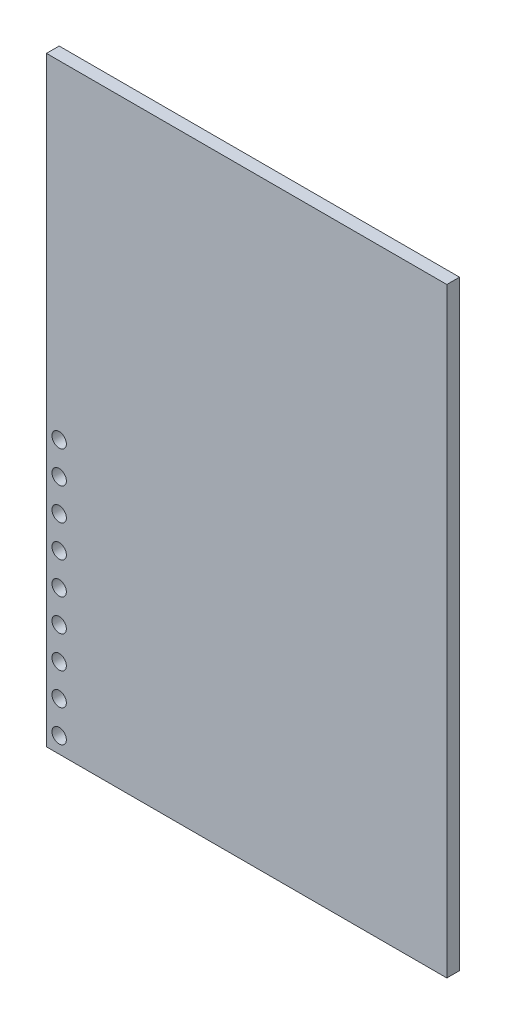
SolidWorks part; units mm, degrees
ref_plane "Front Plane" through (0, 0, 0) normal (0, 0, 1) x (1, 0, 0)
ref_plane "Top Plane" through (0, 0, 0) normal (0, 1, 0) x (1, 0, 0)
ref_plane "Right Plane" through (0, 0, 0) normal (1, 0, 0) x (0, 0, -1)
sketch "Sketch1" plane through (0, 0, 0) normal (0, 1, 0) x (1, 0, 0)
  line L1 (0, 0) -> (100, 0)
  line L2 (0, 0) -> (0, 3.175)
  line L3 (0, 3.175) -> (100, 3.175)
  line L4 (100, 0) -> (100, 3.175)
  dimension "D1" = 100
  dimension "D2" = 3.175
extrude "Boss-Extrude1" add sketch "Sketch1" along normal blind 150
sketch "Sketch2" plane through (0, 0, 0) normal (0, 0, 1) x (1, 0, 0)
  line L0 (6.35, 8) -> (0, 8) construction
  line L5 (0, 0) -> (6.35, 0)
  line L6 (0, 0) -> (0, 16)
  line L8 (6.35, 0) -> (6.35, 16) construction
  line L9 (6.35, 16) -> (0, 16) construction
  line L10 (6.35, 16) -> (6.35, 24) construction
  line L11 (6.35, 24) -> (0, 24) construction
  line L12 (0, 150) -> (0, 0) construction
  line L13 (0, 24) -> (0, 48)
  line L14 (0, 150) -> (0, 0) construction
  line L15 (0, 48) -> (11.1036, 48)
  line L16 (0, 24) -> (0, 32)
  line L17 (0, 32) -> (0, 40)
  line L18 (0, 40) -> (0, 48)
  circle A4 centre (3.175, 4) radius 1.8
  circle A5 centre (3.175, 12) radius 1.8
  circle A6 centre (3.175, 20) radius 1.8
  circle A7 centre (3.175, 44) radius 1.8
  circle A8 centre (3.175, 36) radius 1.8
  circle A9 centre (3.175, 28) radius 1.8
  circle A10 centre (3.175, 68) radius 1.8
  circle A11 centre (3.175, 60) radius 1.8
  circle A12 centre (3.175, 52) radius 1.8
  dimension "D5" = 24
  dimension "D6" = 4
  dimension "D7" = 8
  dimension "D3" = 8
  dimension "D4" = 3.6
  dimension "D1" = 6.35
  dimension "D2" = 8
  dimension "D8" = 3.175
  dimension "D9" = 8
extrude "Cut-Extrude2" cut sketch "Sketch2" against normal blind 5 contours A10
extrude "Cut-Extrude3" cut sketch "Sketch2<14>" against normal blind 5 contours A11
sketch "Sketch2<14>" plane through (0, 0, 0) normal (0, 0, 1) x (1, 0, 0) same geometry as "Sketch2"
extrude "Cut-Extrude4" cut sketch "Sketch2<15>" against normal blind 5 contours A12
sketch "Sketch2<15>" plane through (0, 0, 0) normal (0, 0, 1) x (1, 0, 0) same geometry as "Sketch2"
extrude "Cut-Extrude5" cut sketch "Sketch2<16>" against normal blind 5 contours A7
sketch "Sketch2<16>" plane through (0, 0, 0) normal (0, 0, 1) x (1, 0, 0) same geometry as "Sketch2"
extrude "Cut-Extrude6" cut sketch "Sketch2<17>" against normal blind 5 contours A8
sketch "Sketch2<17>" plane through (0, 0, 0) normal (0, 0, 1) x (1, 0, 0) same geometry as "Sketch2"
extrude "Cut-Extrude7" cut sketch "Sketch2<18>" against normal blind 5 contours A9
sketch "Sketch2<18>" plane through (0, 0, 0) normal (0, 0, 1) x (1, 0, 0) same geometry as "Sketch2"
extrude "Cut-Extrude8" cut sketch "Sketch2<19>" against normal blind 5 contours A6
sketch "Sketch2<19>" plane through (0, 0, 0) normal (0, 0, 1) x (1, 0, 0) same geometry as "Sketch2"
extrude "Cut-Extrude9" cut sketch "Sketch2<20>" against normal blind 5 contours A5
sketch "Sketch2<20>" plane through (0, 0, 0) normal (0, 0, 1) x (1, 0, 0) same geometry as "Sketch2"
extrude "Cut-Extrude10" cut sketch "Sketch2<21>" against normal blind 5 contours A4
sketch "Sketch2<21>" plane through (0, 0, 0) normal (0, 0, 1) x (1, 0, 0) same geometry as "Sketch2"
